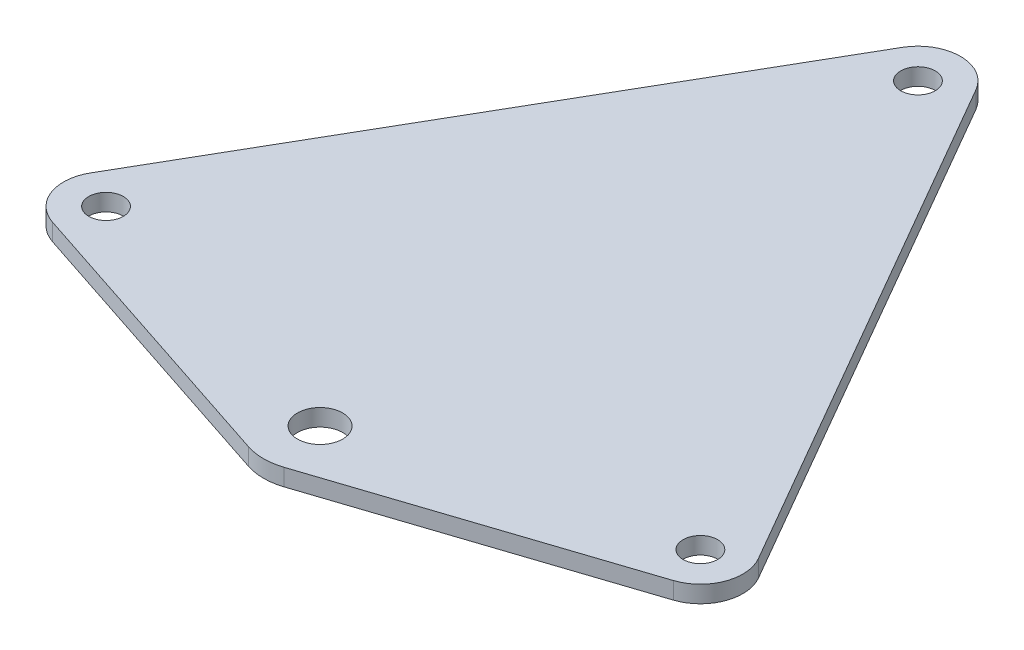
SolidWorks part; units mm, degrees
ref_plane "Front Plane" through (0, 0, 0) normal (0, 0, 1) x (1, 0, 0)
ref_plane "Top Plane" through (0, 0, 0) normal (0, 1, 0) x (1, 0, 0)
ref_plane "Right Plane" through (0, 0, 0) normal (1, 0, 0) x (0, 0, -1)
sketch "Sketch1" plane through (0, 0, 0) normal (0, 1, 0) x (1, 0, 0)
  line L0 (0, 60.6218) -> (-52.5, -30.3109) construction
  line L1 (-52.5, -30.3109) -> (52.5, -30.3109) construction
  line L2 (52.5, -30.3109) -> (0, 60.6218) construction
  line L3 (-6.4952, 64.3718) -> (-58.9952, -26.5609)
  line L4 (-52.5, -37.8109) -> (52.5, -37.8109)
  line L5 (6.4952, 64.3718) -> (58.9952, -26.5609)
  line L6 (0, 60.6218) -> (0, 0) construction
  line L7 (0, 0) -> (-52.5, -30.3109) construction
  line L8 (0, 0) -> (52.5, -30.3109) construction
  line L9 (0, 0) -> (0, -45) construction
  line L10 (-54.8499, -37.4332) -> (-3.1332, -54.4965)
  line L11 (3.1332, -54.4965) -> (54.8499, -37.4332)
  line L12 (-19.1038, 57.533) -> (-6.1134, 50.033) construction
  line L13 (-40.2731, -45.3109) -> (-40.2731, -30.3109) construction
  circle A0 centre (0, 60.6218) radius 7.5 construction
  circle A1 centre (52.5, -30.3109) radius 7.5 construction
  circle A2 centre (-52.5, -30.3109) radius 7.5 construction
  arc A3 (-52.5, -37.8109) -> (-58.9952, -26.5609) centre (-52.5, -30.3109) cw
  arc A4 (58.9952, -26.5609) -> (52.5, -37.8109) centre (52.5, -30.3109) cw
  arc A5 (6.4952, 64.3718) -> (-6.4952, 64.3718) centre (0, 60.6218) ccw
  circle A6 centre (0, 60.6218) radius 3.05
  circle A7 centre (52.5, -30.3109) radius 3.05
  circle A8 centre (-52.5, -30.3109) radius 3.05
  circle A9 centre (0, -45) radius 10 construction
  arc A10 (-3.1332, -54.4965) -> (3.1332, -54.4965) centre (0, -45) ccw
  circle A11 centre (0, -45) radius 4
  arc A12 (0, 60.6218) -> (-29.9926, -52.6825) centre (0, 0) ccw construction
  circle A13 centre (-19.1038, 57.533) radius 6 construction
  circle A14 centre (-40.2731, -45.3109) radius 6 construction
  dimension "D2" = 15
  dimension "D3" = 6.1
  dimension "D4" = 20
  dimension "D6" = 8
  dimension "D7" = 12
  dimension "D1" = 105
  dimension "D5" = 45
  dimension "D8" = 15
extrude "Boss-Extrude1" add sketch "Sketch1" along normal blind 3 contours L5 A5 L3 A3 L4 A4 A8 A7 A6 | L10 A10 L11 A4 L4 A3 A11 region at (0, 0, 0) region at (0, 0, 38.9219)
